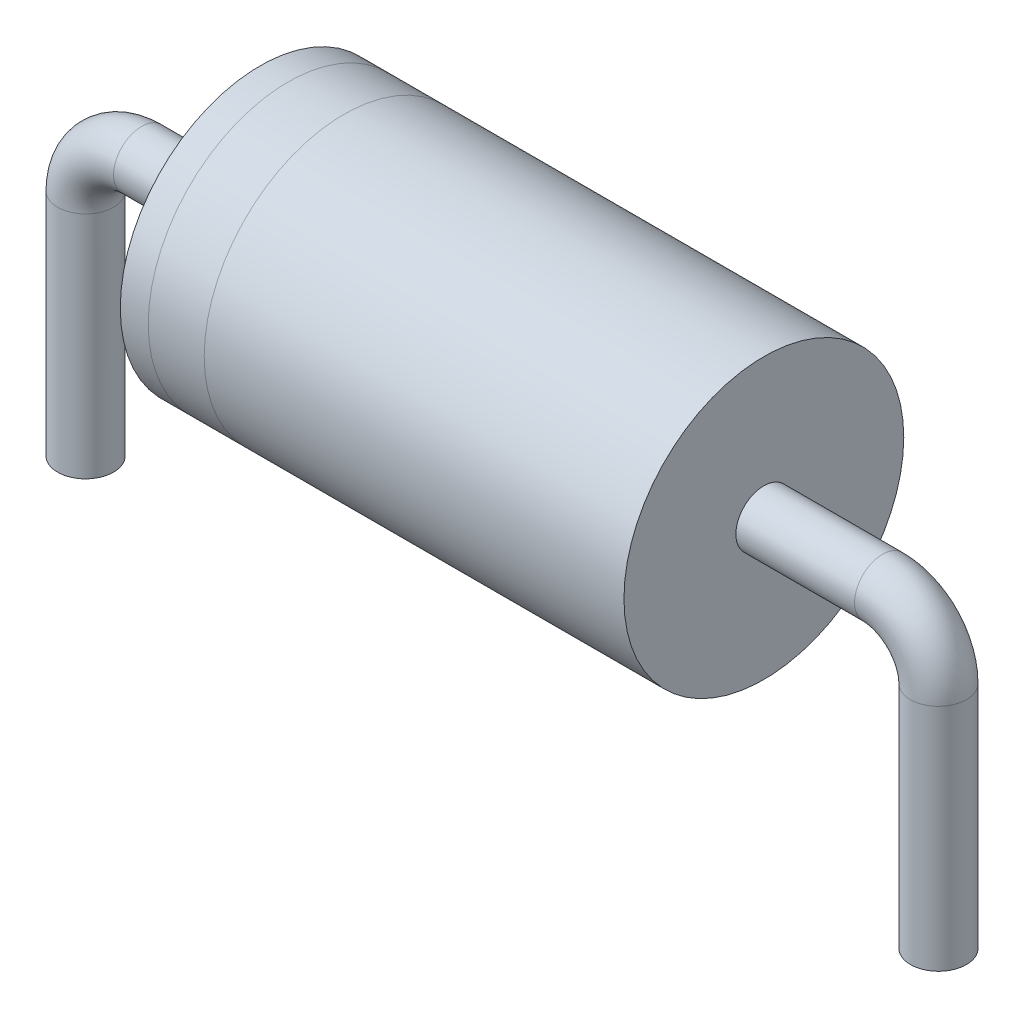
SolidWorks part; units mm, degrees
ref_plane "Спереди" through (0, 0, 0) normal (0, 0, 1) x (1, 0, 0)
ref_plane "Сверху" through (0, 0, 0) normal (0, 1, 0) x (1, 0, 0)
ref_plane "Справа" through (0, 0, 0) normal (1, 0, 0) x (0, 0, -1)
sketch "Эскиз1" plane through (0, 0, 0) normal (1, 0, 0) x (0, 0, -1)
  circle A0 centre (0, 0) radius 2.5
  dimension "D1" = 5
extrude "Бобышка-Вытянуть1" add sketch "Эскиз1" along normal blind 4.5 and the other way blind 4.5
sketch "Эскиз2" plane through (0, 0, 0) normal (0, 0, 1) x (1, 0, 0)
  line L0 (-6.62, 0) -> (6.62, 0)
  line L1 (7.62, -1) -> (7.62, -5.1)
  line L2 (0, -50) -> (0, 50) construction
  line L3 (-7.62, -1) -> (-7.62, -5.1)
  arc A0 (6.62, 0) -> (7.62, -1) centre (6.62, -1) cw
  arc A1 (-6.62, 0) -> (-7.62, -1) centre (-6.62, -1) ccw
  point P8 (0, 0)
  point P9 (7.62, 0)
  point P11 (0, 0)
  dimension "D2" = 1
  dimension "D1" = 7.62
  dimension "D3" = 5.1
sketch "Эскиз3" plane through (4.5, 0, 0) normal (1, 0, 0) x (0, 0, -1)
  circle A0 centre (0, 0) radius 0.5
sweep "По траектории1" add profiles "Эскиз3" path "Эскиз2"
sketch "Эскиз4" plane through (0, 0, 0) normal (0, 0, 1) x (1, 0, 0)
  line L1 (-4, 7.854) -> (-3, 7.854)
  line L2 (-4, 7.854) -> (-4, -7.854)
  line L3 (-4, -7.854) -> (-3, -7.854)
  line L4 (-3, 7.854) -> (-3, -7.854)
  point P4 (0, 0)
  point P5 (0, 0)
  point P8 (0, 0)
  point P9 (0, 0)
  dimension "D1" = 15.708
wrap "Перенос1" sketch "Эскиз4" wrap type scribe source sketch "Эскиз4" face at (-4.5, 0, -2.5)
